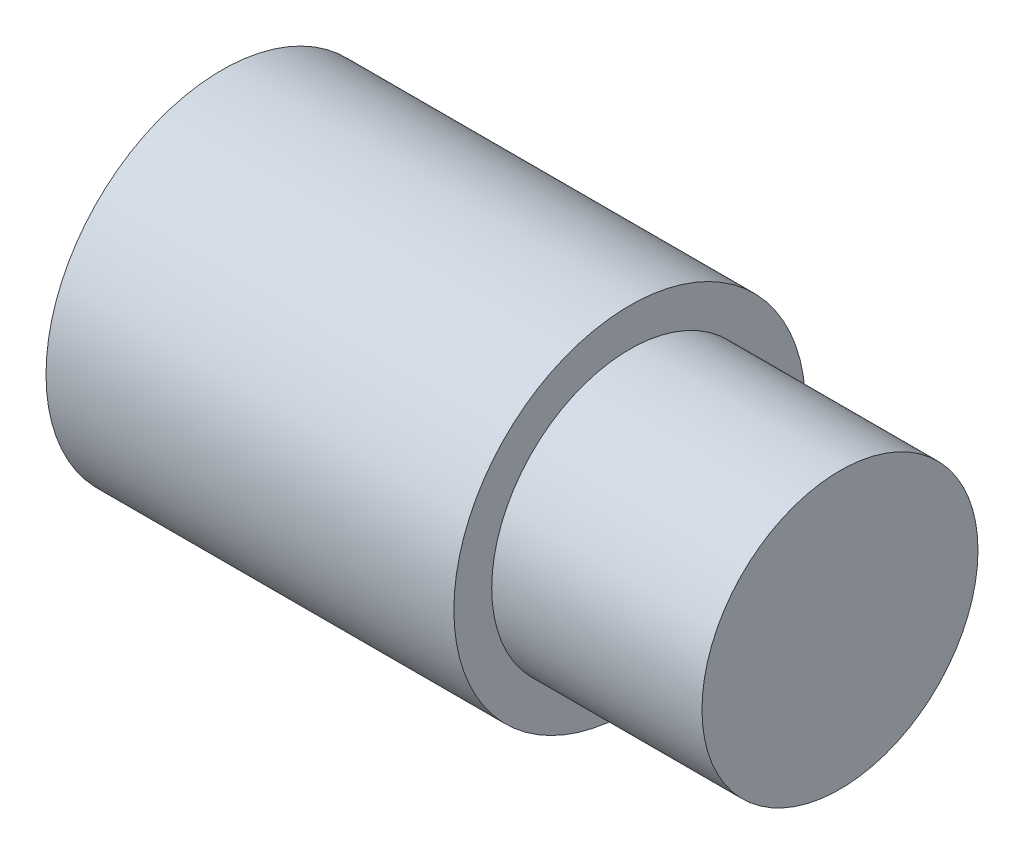
SolidWorks part; units mm, degrees
ref_plane "Front Plane" through (0, 0, 0) normal (0, 0, 1) x (1, 0, 0)
ref_plane "Top Plane" through (0, 0, 0) normal (0, 1, 0) x (1, 0, 0)
ref_plane "Right Plane" through (0, 0, 0) normal (1, 0, 0) x (0, 0, -1)
sketch "Conn_T6_ORB8 Sketch" plane through (0, 0, 0) normal (0, 0, 1) x (1, 0, 0)
  line L0 (-1000, 0) -> (1000, 0) construction
  line L1 (13.3, 0) -> (13.3, 8.73)
  line L2 (13.3, 8.73) -> (0, 8.73)
  line L3 (0, 8.73) -> (0, 11.124)
  line L4 (0, 11.124) -> (-25.8, 11.124)
  line L5 (-25.8, 11.124) -> (-25.8, 0)
  line L6 (-25.8, 0) -> (13.3, 0)
revolve "Conn_T6_ORB8" add sketch "Conn_T6_ORB8 Sketch" angle 360 about L0
ref_axis "Engine Axis" through (15.255, 0, 0) along (-1, 0, 0)
sketch "Socket Sketch" plane through (0, 0, 0) normal (0, 0, 1) x (1, 0, 0)
  line L0 (-1000, 0) -> (1000, 0) construction
  line L1 (-26.8, 0) -> (-26.8, 4.7625)
  line L2 (-26.8, 4.7625) -> (-9, 4.7625)
  line L3 (-9, 4.7625) -> (-9, 0)
  line L4 (-9, 0) -> (-26.8, 0)
revolve "Socket" cut sketch "Socket Sketch" angle 360 about L0
